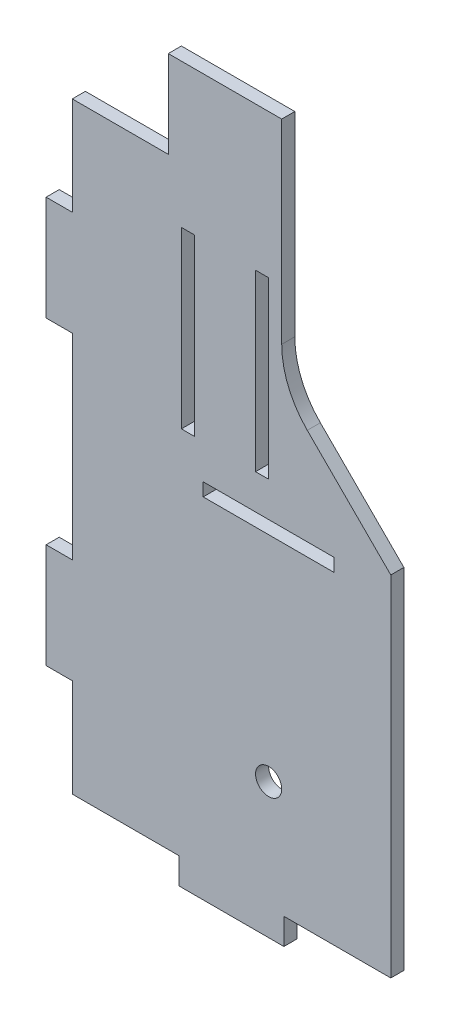
SolidWorks part; units mm, degrees
ref_plane "Front Plane" through (0, 0, 0) normal (0, 0, 1) x (1, 0, 0)
ref_plane "Top Plane" through (0, 0, 0) normal (0, 1, 0) x (1, 0, 0)
ref_plane "Right Plane" through (0, 0, 0) normal (1, 0, 0) x (0, 0, -1)
sketch "Sketch1" plane through (0, 0, 0) normal (0, 0, 1) x (1, 0, 0)
  line L0 (-73, 138) -> (-73, 0)
  line L1 (-73, 0) -> (0, 0)
  line L2 (0, 0) -> (0, 77)
  line L3 (0, 77) -> (-31, 77)
  line L4 (-31, 77) -> (-31, 138)
  line L5 (-31, 138) -> (-73, 138)
  dimension "D1" = 77
  dimension "D2" = 73
  dimension "D3" = 42
  dimension "D4" = 138
extrude "BaseShape" add sketch "Sketch1" along normal blind 3
sketch "Sketch2" plane through (0, 0, 3) normal (0, 0, 1) x (1, 0, 0)
  line L1 (-73, 0) -> (0, 0) construction
  line L2 (0, 0) -> (0, 77) construction
  circle A0 centre (-28, 25) radius 3
  dimension "D1" = 6
  dimension "D2" = 28
  dimension "D3" = 25
extrude "ShaftHoles" cut sketch "Sketch2" against normal through all
sketch "Sketch4" plane through (0, 0, 3) normal (0, 0, 1) x (1, 0, 0)
  line L0 (-31, 77) -> (-31, 138) construction
  line L1 (0, 77) -> (-31, 77)
  line L2 (0, 77) -> (0, 80)
  line L3 (0, 80) -> (-31, 80) construction
  line L4 (-31, 77) -> (-31, 80)
  line L5 (-73, 138) -> (-73, 0) construction
  line L6 (-73, 115.5) -> (-79, 115.5)
  line L7 (-73, 115.5) -> (-73, 91.5)
  line L8 (-73, 91.5) -> (-79, 91.5)
  line L9 (-79, 115.5) -> (-79, 91.5)
  line L10 (-73, 0) -> (0, 0) construction
  line L11 (-73, 46.5) -> (-79, 46.5)
  line L12 (-73, 46.5) -> (-73, 22.5)
  line L13 (-73, 22.5) -> (-79, 22.5)
  line L14 (-79, 46.5) -> (-79, 22.5)
  line L15 (-48.5, 0) -> (-24.5, 0)
  line L16 (-48.5, 0) -> (-48.5, -6)
  line L17 (-48.5, -6) -> (-24.5, -6)
  line L18 (-24.5, 0) -> (-24.5, -6)
  line L19 (-73, 115.5) -> (-73, 138) construction
  line L20 (-73, 22.5) -> (-73, 0) construction
  line L21 (-73, 69) -> (-73, 91.5) construction
  line L22 (-73, 46.5) -> (-73, 69) construction
  line L23 (-73, 0) -> (-73, 69) construction
  line L24 (-48.5, 0) -> (-73, 0) construction
  line L25 (-24.5, 0) -> (0, 0) construction
  line L26 (-25, 80) -> (0, 80)
  line L27 (-31, 138) -> (-25, 138)
  line L28 (-31, 138) -> (-31, 80)
  line L29 (-31, 80) -> (-25, 80) construction
  line L30 (-25, 138) -> (-25, 80)
  point P23 (-73, 69)
  point P28 (-73, 34.5)
  point P32 (-73, 34.5)
  dimension "D1" = 3
  dimension "D2" = 6
  dimension "D3" = 24
  dimension "D4" = 6
extrude "Fingers" add sketch "Sketch4" against normal up to surface (3 mm away) up to face at (-25, 25, 0)
sketch "Sketch5" plane through (0, 0, 3) normal (0, 0, 1) x (1, 0, 0)
  line L0 (0, 0) -> (0, 80) construction
  line L1 (-43, 77) -> (-13, 77)
  line L2 (-43, 77) -> (-43, 74)
  line L3 (-43, 74) -> (-13, 74)
  line L4 (-13, 77) -> (-13, 74)
  line L7 (-48, 125) -> (-45, 125)
  line L8 (-48, 125) -> (-48, 85)
  line L9 (-48, 85) -> (-45, 85)
  line L10 (-45, 125) -> (-45, 85)
  line L11 (0, 80) -> (-25, 80) construction
  line L12 (-25, 80) -> (-25, 138) construction
  line L13 (-31, 125) -> (-28, 125)
  line L14 (-31, 125) -> (-31, 85)
  line L15 (-31, 85) -> (-28, 85)
  line L16 (-28, 125) -> (-28, 85)
  point P20 (-29.5, 85)
  point P21 (-65, 85)
  dimension "D1" = 3
  dimension "D2" = 3
  dimension "D3" = 30
  dimension "D4" = 13
  dimension "D5" = 14
  dimension "D6" = 3
  dimension "D7" = 3
  dimension "D8" = 3
  dimension "D9" = 40
  dimension "D10" = 8
extrude "Grooves" cut sketch "Sketch5" against normal through all
chamfer "Chamfer1" distance 25 angle 45 1 edges at (-25, 80, 1.5)
fillet "Fillet2" radius 20 1 edges at (-25, 105, 1.5)
sketch "Sketch6" plane through (0, 138, 0) normal (0, 1, 0) x (1, 0, 0)
  line L0 (-25, -3) -> (-73, -3) construction
  line L1 (-25, 0) -> (-51, 0)
  line L2 (-25, 0) -> (-25, -3)
  line L3 (-25, -3) -> (-51, -3)
  line L4 (-51, 0) -> (-51, -3)
  dimension "D1" = 22
extrude "MarbleChute" add sketch "Sketch6" along normal blind 20
